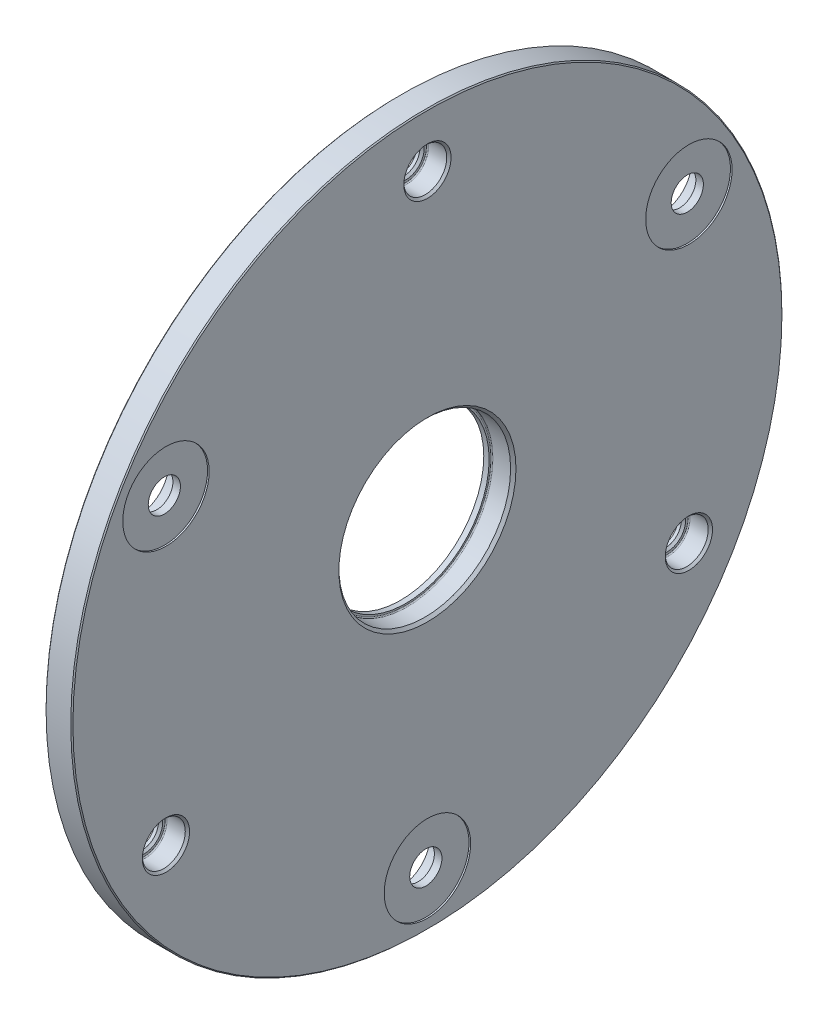
SolidWorks part; units mm, degrees
material "1.7225 (42CrMo4)"
ref_plane "前基準面" through (0, 0, 0) normal (0, 0, 1) x (1, 0, 0)
ref_plane "上基準面" through (0, 0, 0) normal (0, 1, 0) x (1, 0, 0)
ref_plane "右基準面" through (0, 0, 0) normal (1, 0, 0) x (0, 0, -1)
sketch "Sketch1" plane through (0, 0, 0) normal (1, 0, 0) x (0, 0, -1)
  line L0 (0, 56.25) -> (0, 0) construction
  line L1 (0, 0) -> (48.7139, -28.125) construction
  line L2 (0, 0) -> (-48.7139, -28.125) construction
  circle A10 centre (0, 0) radius 28.75
  circle A11 centre (0, 56.25) radius 27.5
  circle A12 centre (0, 0) radius 83.75
  circle A13 centre (48.7139, -28.125) radius 27.5
  circle A14 centre (-48.7139, -28.125) radius 27.5
  dimension "D1" = 57.5
  dimension "D2" = 55
  dimension "D3" = 167.5
  dimension "D4" = 120
  dimension "D5" = 120
sketch "Sketch2" plane through (0, 0, 0) normal (1, 0, 0) x (0, 0, -1)
  circle A0 centre (0, 0) radius 56.25 construction
  circle A1 centre (0, 0) radius 66.25
  circle A2 centre (0, 0) radius 16
  dimension "D1" = 10
  dimension "D2" = 32
extrude "Boss-Extrude1" add sketch "Sketch2" against normal blind 5
sketch "Sketch4" plane through (0, 0, 0) normal (1, 0, 0) x (0, 0, -1)
  circle A1 centre (0, 56.25) radius 27.5 construction
  circle A2 centre (0, 56.25) radius 4 construction
  circle A3 centre (0, 56.25) radius 4
  circle A4 centre (0, 56.25) radius 3 construction
  circle A5 centre (0, 56.25) radius 3
  circle A6 centre (0, 56.25) radius 27.5 construction
  dimension "D1" = 8
  dimension "D3" = 6
  dimension "D2" = 0
  dimension "D4" = 0
extrude "Cut-Extrude1" cut sketch "Sketch4" against normal up to surface (5 mm away) contours A5 region at (0, 56.25, 0) up to face at (-5, 0, -16)
extrude "Cut-Extrude2" cut sketch "Sketch4<3>" against normal offset from surface (4 mm away) 1 up to face at (-5, 56.25, -3)
sketch "Sketch4<3>" plane through (0, 0, 0) normal (1, 0, 0) x (0, 0, -1) same geometry as "Sketch4"
chamfer "Chamfer1" distance 0.4 angle 45 2 edges at (0, 56.25, -4) (-4, 56.25, -3)
fillet "Fillet3" radius 0.2 1 edges at (-4, 56.25, -4)
sketch "Sketch5" plane through (0, 0, 0) normal (1, 0, 0) x (0, 0, -1)
  line L0 (0, 56.25) -> (0, 0) construction
  line L1 (0, 0) -> (48.7139, -28.125) construction
  line L2 (0, 56.25) -> (48.7139, -28.125) construction
  line L3 (0, 0) -> (48.7139, 28.125) construction
  circle A0 centre (0, 0) radius 56.25 construction
  circle A1 centre (48.7139, 28.125) radius 3
  circle A2 centre (48.7139, 28.125) radius 6 construction
  circle A3 centre (48.7139, 28.125) radius 8 construction
  circle A4 centre (48.7139, 28.125) radius 8.05
  circle A5 centre (0, 56.25) radius 3 construction
  dimension "D1" = 6
  dimension "D2" = 12
  dimension "D3" = 16
  dimension "D4" = 0.05
extrude "Cut-Extrude3" cut sketch "Sketch5" against normal blind 0.3 contours A1 | A3 A1 region at (0, 28.125, -48.7139) region at (0, 28.125, -40.8916)
hole_wizard "CBORE for M6 SBHCS1" positions "Sketch6" profile "Sketch7" counterbore size "M6" standard "ANSI Metric" end condition through all
sketch "Sketch6" plane through (-5, 0, 0) normal (-1, 0, 0) x (0, 0, 1)
  point P0 (-48.7139, 28.125)
sketch "Sketch7" plane through (-5, 28.125, -48.7139) normal (0, 1, 0) x (0, 0, 1)
  line L0 (0, 0) -> (0, 5)
  line L1 (0, 5) -> (3, 5)
  line L3 (3, 5) -> (3, 3.3)
  line L4 (3, 3.3) -> (5.5, 3.3)
  line L5 (5.5, 3.3) -> (5.5, 0)
  line L7 (5.5, 0) -> (0, 0)
  line L11 (0, -6.35) -> (0, 107.95) construction
  dimension "Thru Hole Dia." = 6
  dimension "Thru Hole Depth" = 5
  dimension "C'Bore Dia." = 11
  dimension "C'Bore Depth" = 3.3
pattern_circular "CirPattern1" count 3 over 360 about axis through (-5, 0, 0) along (1, 0, 0) of "Cut-Extrude1", "Cut-Extrude2", "Chamfer1", "Cut-Extrude3", "CBORE for M6 SBHCS1", "Fillet3" reverse direction yes
sketch "Sketch8" plane through (0, 0, 0) normal (1, 0, 0) x (0, 0, -1)
  circle A0 centre (0, 0) radius 15.5
  circle A1 centre (0, 0) radius 16 construction
  circle A2 centre (0, 0) radius 16
  dimension "D1" = 31
extrude "Boss-Extrude2" add sketch "Sketch8" along normal blind 1 from surface starting at face at (-5, 28.125, 54.2139)
fillet "Fillet2" radius 0.2 1 edges at (-4, 0, -16)
chamfer "Chamfer2" distance 0.5 angle 45 1 edges at (0, 0, -16)
chamfer "Chamfer3" distance 0.2 angle 45 2 edges at (0, 0, -66.25) (-5, 0, -66.25)
